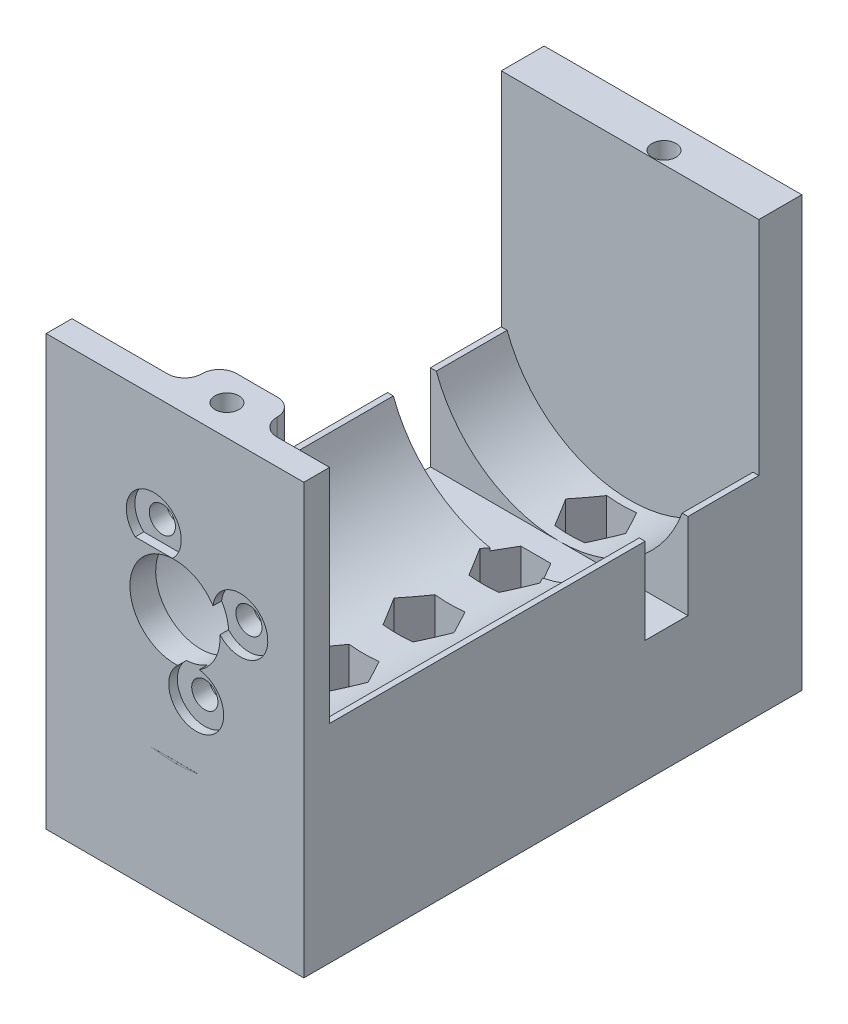
SolidWorks part; units mm, degrees
ref_plane "Front Plane" through (0, 0, 0) normal (0, 0, 1) x (1, 0, 0)
ref_plane "Top Plane" through (0, 0, 0) normal (0, 1, 0) x (1, 0, 0)
ref_plane "Right Plane" through (0, 0, 0) normal (1, 0, 0) x (0, 0, -1)
sketch "Sketch1" plane through (0, 0, 0) normal (0, 0, 1) x (1, 0, 0)
  line L1 (-15, -15) -> (15, -15)
  line L5 (-15, -15) -> (-15, -5.25)
  line L6 (15, -15) -> (15, 13)
  line L9 (-15, 13) -> (15, 13)
  line L11 (0, -5.25) -> (-15, -5.25)
  line L12 (0, 5.25) -> (-15, 5.25)
  line L13 (-15, 5.25) -> (-15, 13)
  line L14 (0, 0) -> (0, 8) construction
  line L15 (2.4721, -7.6085) -> (-2.4721, 7.6085) construction
  line L16 (0, 0) -> (7.6085, 2.4721) construction
  arc A0 (0, -5.25) -> (5.25, 0) centre (0, 0) ccw
  circle A1 centre (0, 0) radius 8 construction
  arc A5 (0, 5.25) -> (5.25, 0) centre (0, 0) cw
  circle A7 centre (-2.4721, 7.6085) radius 1.525
  circle A10 centre (7.6085, 2.4721) radius 1.525
  circle A11 centre (2.4721, -7.6085) radius 1.525
  dimension "D2" = 10.5
  dimension "D5" = 16
  dimension "D6" = 18
  dimension "D8" = 3.05
  dimension "D1" = 30
  dimension "D3" = 28
  dimension "D7" = 90
extrude "Boss-Extrude1" add sketch "Sketch1" along normal blind 3
sketch "Sketch2" plane through (0, 0, 3) normal (0, 0, 1) x (1, 0, 0)
  line L0 (-15, -15) -> (-15, -5.25)
  line L2 (-15, -15) -> (-15, -29.425)
  line L3 (-15, -29.425) -> (15, -29.425)
  line L4 (15, -15) -> (15, -29.425)
  line L6 (15, -15) -> (15, -5.25)
  line L8 (-15, -5.25) -> (-14.3178, -5.25)
  line L9 (0, -5.25) -> (-15, -5.25) construction
  line L10 (-14.3178, -5.25) -> (16.0436, -5.25) construction
  line L11 (15, -5.25) -> (14.3178, -5.25)
  arc A0 (-14.3178, -5.25) -> (14.3178, -5.25) centre (0, 0) ccw
  dimension "D2" = 30.5
  dimension "D4" = 15.25
  dimension "D1" = 14.425
  dimension "D3" = 14.425
extrude "Boss-Extrude2" add sketch "Sketch2" against normal blind 53
sketch "Sketch3" plane through (0, -29.425, 0) normal (0, -1, 0) x (-1, 0, 0)
  line L0 (0, -3) -> (0, 50) construction
  line L1 (15, -3) -> (-15, -3) construction
  line L2 (15, 50) -> (-15, 50) construction
  circle A0 centre (0, 46) radius 1.55
  circle A1 centre (0, 36) radius 1.55
  circle A2 centre (0, 26) radius 1.55
  circle A3 centre (0, 16) radius 1.55
  circle A4 centre (0, 6) radius 1.55
  dimension "D1" = 3.1
  dimension "D2" = 4
  dimension "D3" = 5
extrude "Cut-Extrude1" cut sketch "Sketch3" against normal through all
sketch "Sketch4" plane through (0, 0, 3) normal (0, 0, 1) x (1, 0, 0)
  line L0 (-2.75, -15) -> (2.694, -15.0102)
  arc A0 (-2.75, -15) -> (2.694, -15.0102) centre (0, 0) ccw
extrude "Boss-Extrude3" add sketch "Sketch4" against normal blind 3 separate body
sketch "Sketch5" plane through (0, -29.425, 0) normal (0, -1, 0) x (-1, 0, 0)
  line L0 (3.493, 36) -> (1.7465, 39.025)
  line L1 (3.493, 46) -> (1.7465, 49.025)
  line L2 (1.7465, 49.025) -> (-1.7465, 49.025)
  line L3 (-1.7465, 49.025) -> (-3.493, 46)
  line L4 (-3.493, 46) -> (-1.7465, 42.975)
  line L5 (-1.7465, 42.975) -> (1.7465, 42.975)
  line L6 (1.7465, 42.975) -> (3.493, 46)
  line L7 (1.7465, 39.025) -> (-1.7465, 39.025)
  line L8 (-1.7465, 39.025) -> (-3.493, 36)
  line L9 (-3.493, 36) -> (-1.7465, 32.975)
  line L10 (-1.7465, 32.975) -> (1.7465, 32.975)
  line L11 (1.7465, 32.975) -> (3.493, 36)
  line L12 (3.493, 26) -> (1.7465, 29.025)
  line L13 (1.7465, 29.025) -> (-1.7465, 29.025)
  line L14 (-1.7465, 29.025) -> (-3.493, 26)
  line L15 (-3.493, 26) -> (-1.7465, 22.975)
  line L16 (-1.7465, 22.975) -> (1.7465, 22.975)
  line L17 (1.7465, 22.975) -> (3.493, 26)
  line L18 (3.493, 16) -> (1.7465, 19.025)
  line L19 (1.7465, 19.025) -> (-1.7465, 19.025)
  line L20 (-1.7465, 19.025) -> (-3.493, 16)
  line L21 (-3.493, 16) -> (-1.7465, 12.975)
  line L22 (-1.7465, 12.975) -> (1.7465, 12.975)
  line L23 (1.7465, 12.975) -> (3.493, 16)
  line L24 (3.493, 6) -> (1.7465, 9.025)
  line L25 (1.7465, 9.025) -> (-1.7465, 9.025)
  line L26 (-1.7465, 9.025) -> (-3.493, 6)
  line L27 (-3.493, 6) -> (-1.7465, 2.975)
  line L28 (-1.7465, 2.975) -> (1.7465, 2.975)
  line L29 (1.7465, 2.975) -> (3.493, 6)
  circle A5 centre (0, 46) radius 3.025 construction
  circle A6 centre (0, 36) radius 3.025 construction
  circle A7 centre (0, 26) radius 3.025 construction
  circle A8 centre (0, 16) radius 3.025 construction
  circle A9 centre (0, 6) radius 3.025 construction
  dimension "D1" = 6.05
  dimension "D2" = 5
extrude "Cut-Extrude2" cut sketch "Sketch5" against normal through all from offset 5 offset against normal yes
sketch "Sketch6" plane through (0, 0, 3) normal (0, 0, 1) x (1, 0, 0)
  circle A1 centre (2.4721, -7.6085) radius 3.2
  circle A4 centre (-2.4721, 7.6085) radius 3.2
  circle A5 centre (7.6085, 2.4721) radius 3.2
  dimension "D1" = 6.4
extrude "Cut-Extrude3" cut sketch "Sketch6" against normal blind 1
sketch "Sketch7" plane through (0, 0, -50) normal (0, 0, -1) x (-1, 0, 0)
  line L0 (15, 13) -> (15, 2.75) construction
  line L1 (-15, -29.425) -> (15, -29.425)
  line L2 (-15, -29.425) -> (-15, 20.575)
  line L3 (-15, 20.575) -> (15, 20.575)
  line L4 (15, -29.425) -> (15, 20.575)
  dimension "D1" = 50
extrude "Boss-Extrude4" add sketch "Sketch7" along normal blind 5
sketch "Sketch9" plane through (-15, 0, 0) normal (-1, 0, 0) x (0, 0, 1)
  line L5 (3, -5.25) -> (-50, -5.25) construction
  line L6 (-41.75, -15.25) -> (-36.75, -15.25)
  line L9 (-41.75, -15.25) -> (-41.75, 4.75)
  line L10 (-41.75, 4.75) -> (-36.75, 4.75)
  line L11 (-36.75, -15.25) -> (-36.75, 4.75)
  line L12 (-41.75, -15.25) -> (-36.75, 4.75) construction
  line L13 (-41.75, 4.75) -> (-36.75, -15.25) construction
  line L14 (3, -5.25) -> (3, -29.425) construction
  point P0 (-39.25, -5.25)
  dimension "D1" = 42.25
  dimension "D2" = 5
  dimension "D3" = 20
extrude "Cut-Extrude6" cut sketch "Sketch9" against normal through all
sketch "Sketch10" plane through (0, -29.425, 0) normal (0, -1, 0) x (-1, 0, 0)
  line L0 (15, 26) -> (-15, 26) construction
  line L1 (15, 55) -> (15, -3) construction
  line L2 (-15, 55) -> (-15, -3) construction
  circle A0 centre (5, 26) radius 7.5
  dimension "D1" = 15
  dimension "D2" = 10
extrude "Cut-Extrude7" cut sketch "Sketch10" against normal blind 5
sketch "Sketch12" plane through (0, 20.575, 0) normal (0, 1, 0) x (1, 0, 0)
  line L0 (-15, 41.75) -> (-15, 50) construction
  line L1 (15, 55) -> (15, -3) construction
  line L2 (-15, 55) -> (15, 55) construction
  line L3 (15, 26) -> (-27.1391, 26) construction
  circle A0 centre (2.5, 51.45) radius 1.4
  dimension "D3" = 2.8
  dimension "D1" = 17.5
  dimension "D2" = 3.55
extrude "Cut-Extrude8" cut sketch "Sketch12" against normal blind 10
sketch "Sketch13" plane through (0, 13, 0) normal (0, 1, 0) x (1, 0, 0)
  line L1 (-15, 0) -> (15, 0)
  line L2 (-15, 0) -> (-15, -3)
  line L3 (-15, -3) -> (15, -3)
  line L4 (15, 0) -> (15, -3)
extrude "Boss-Extrude5" add sketch "Sketch13" along normal up to surface (7.575 mm away) up to face at (2.5, 20.575, -50.05)
sketch "Sketch14" plane through (0, 0, 3) normal (0, 0, 1) x (1, 0, 0)
  line L0 (0, 5.25) -> (-15, 5.25)
  line L1 (-15, 5.25) -> (-15, -5.25)
  line L2 (-15, -5.25) -> (0, -5.25)
  arc A0 (0, 5.25) -> (0, -5.25) centre (0, 0) ccw
extrude "Boss-Extrude6" add sketch "Sketch14" against normal up to surface (3 mm away) up to face at (0.525, -0.2421, 0)
sketch "Sketch15" plane through (0, 20.575, 0) normal (0, 1, 0) x (1, 0, 0)
  line L0 (15, 55) -> (15, -3) construction
  line L1 (15, 26) -> (-39.5686, 26) construction
  line L3 (-1.8729, -2.95) -> (6.8729, -2.95)
  line L4 (-1.8729, -2.95) -> (-1.8729, 4.05)
  line L5 (-1.8729, 4.05) -> (6.8729, 4.05)
  line L6 (6.8729, -2.95) -> (6.8729, 4.05)
  line L7 (-1.8729, -2.95) -> (6.8729, 4.05) construction
  line L8 (-1.8729, 4.05) -> (6.8729, -2.95) construction
  circle A1 centre (2.5, 0.55) radius 1.4
  dimension "D1" = 3.5
extrude "Boss-Extrude7" add sketch "Sketch15" against normal blind 5
sketch "Sketch16" plane through (0, 20.575, 0) normal (0, 1, 0) x (1, 0, 0)
  circle A0 centre (2.5, 0.55) radius 1.4
extrude "Cut-Extrude9" cut sketch "Sketch16" against normal blind 7
fillet "Fillet1" radius 2 5 edges at (-0.3302, 15.575, 0) (6.8729, 18.075, 0) (6.8729, 18.075, -4.05) (-1.8729, 18.075, -4.05) (-1.8729, 18.075, 0)
